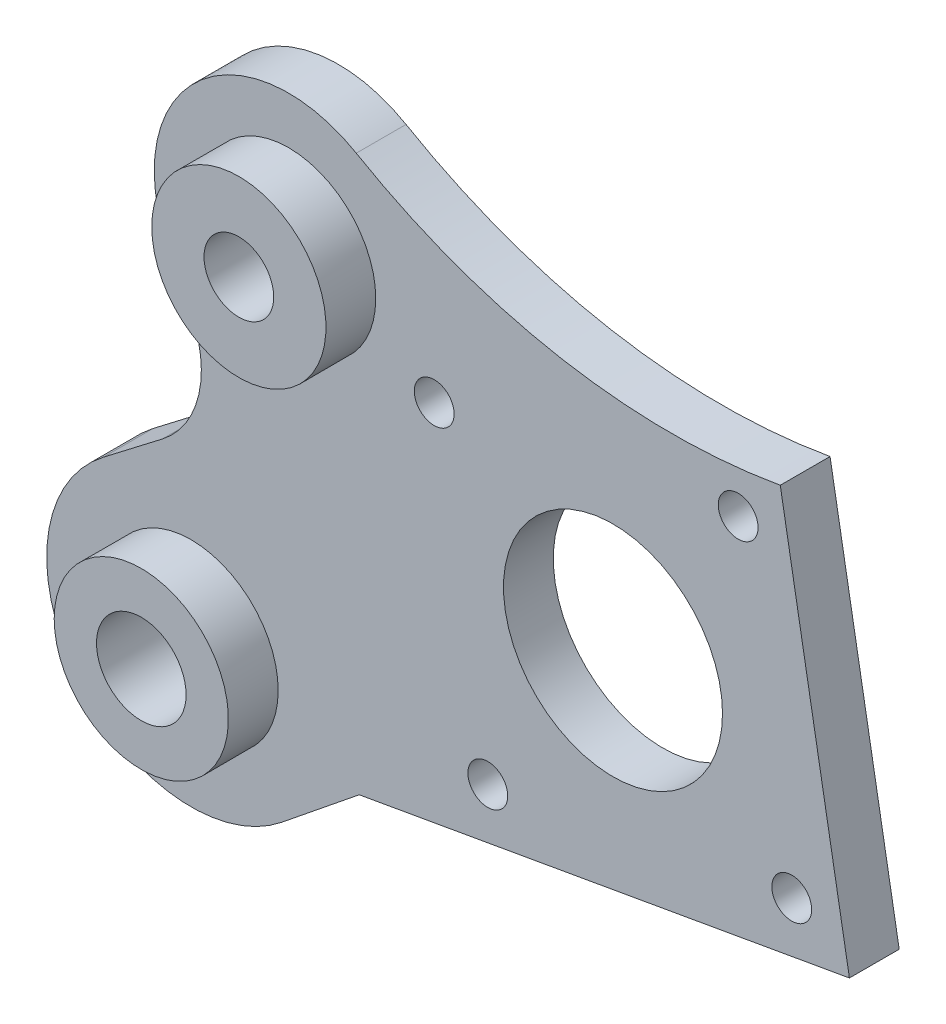
SolidWorks part; units mm, degrees
material "ABS"
ref_plane "Спереди" through (0, 0, 0) normal (0, 0, 1) x (1, 0, 0)
ref_plane "Сверху" through (0, 0, 0) normal (0, 1, 0) x (1, 0, 0)
ref_plane "Справа" through (0, 0, 0) normal (1, 0, 0) x (0, 0, -1)
sketch "Sketch1" plane through (0, 0, 0) normal (0, 0, 1) x (1, 0, 0)
  line L0 (-12.0689, -6.0492) -> (-9.8284, -10.5191)
  line L1 (-12.6807, -22.9335) -> (-18.6271, -27.4964)
  line L2 (-0.6913, -50.2819) -> (7.0893, -44)
  line L3 (7.0893, -44) -> (56.3297, -35.3176)
  line L4 (56.3297, -35.3176) -> (49.3838, 4.0747)
  line L5 (7.0893, -44) -> (51.1124, -44) construction
  line L6 (49.3838, 4.0747) -> (9.2302, -3.0054) construction
  circle A0 centre (0, 0) radius 3.5
  circle A1 centre (-9.8, -39) radius 4.5
  arc A2 (-18.6271, -27.4964) -> (-0.6913, -50.2819) centre (-9.8, -39) ccw
  arc A3 (6.7934, 11.6662) -> (-12.0689, -6.0492) centre (0, 0) ccw
  arc A4 (-12.6807, -22.9335) -> (-9.8284, -10.5191) centre (-18.7683, -15) ccw
  arc A5 (6.7934, 11.6662) -> (49.3838, 4.0747) centre (38.4573, 66.042) ccw
  dimension "D1" = 9
  dimension "D2" = 7
  dimension "D3" = 9.8
  dimension "D4" = 39
  dimension "D5" = 10
  dimension "D6" = 10
  dimension "D7" = 10
  dimension "D14" = 5
  dimension "D8" = 15
  dimension "D9" = 5
  dimension "D10" = 50
  dimension "D11" = 10
  dimension "D12" = 40
  dimension "D13" = 10
extrude "Boss-Extrude1" add sketch "Sketch1" against normal blind 5
sketch "Sketch2" plane through (0, 0, 0) normal (0, 0, -1) x (-1, 0, 0)
  circle A0 centre (0, 0) radius 8.75
  circle A1 centre (9.8, -39) radius 8.75
  circle A2 centre (0, 0) radius 3.5
  circle A3 centre (9.8, -39) radius 4.5
  dimension "D1" = 17.5
  dimension "D2" = 17.5
extrude "Boss-Extrude2" add sketch "Sketch2" against normal blind 5
sketch "Sketch4" plane through (0, 0, 0) normal (0, 0, 1) x (1, 0, 0)
  line L0 (20.0084, -36.6449) -> (50.5375, -31.2618) construction
  line L1 (14.6253, -6.1158) -> (45.1544, -0.7328) construction
  line L2 (7.0893, -44) -> (56.3297, -35.3176) construction
  line L3 (45.1544, -0.7328) -> (50.5375, -31.2618) construction
  line L4 (56.3297, -35.3176) -> (49.3838, 4.0747) construction
  circle A0 centre (14.6253, -6.1158) radius 2
  circle A1 centre (20.0084, -36.6449) radius 2
  circle A2 centre (50.5375, -31.2618) radius 2
  circle A3 centre (45.1544, -0.7328) radius 2
  circle A4 centre (32.5814, -18.6888) radius 11
  dimension "D1" = 4
  dimension "D2" = 22
  dimension "D6" = 15.5
  dimension "D3" = 31
  dimension "D4" = 31
  dimension "D5" = 15.5
  dimension "D7" = 5
  dimension "D8" = 5
extrude "Cut-Extrude1" cut sketch "Sketch4" against normal through all
